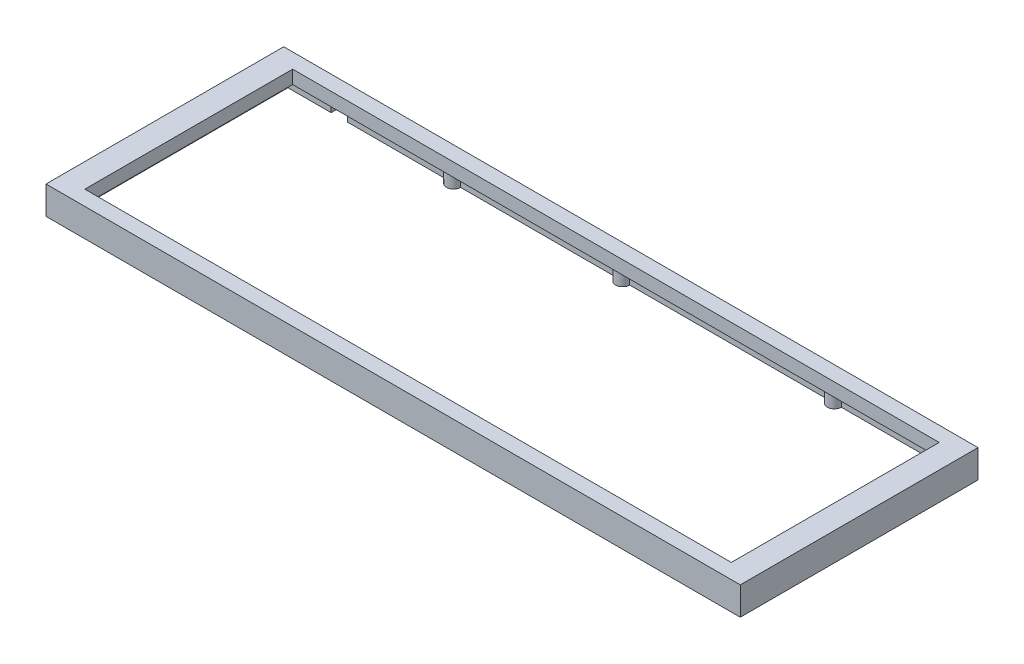
SolidWorks part; units mm, degrees
ref_plane "Front Plane" through (0, 0, 0) normal (0, 0, 1) x (1, 0, 0)
ref_plane "Top Plane" through (0, 0, 0) normal (0, 1, 0) x (1, 0, 0)
ref_plane "Right Plane" through (0, 0, 0) normal (1, 0, 0) x (0, 0, -1)
sketch "Sketch1" plane through (0, 0, 0) normal (0, 1, 0) x (1, 0, 0)
  line L1 (0, 0) -> (363.9, 0)
  line L2 (0, 0) -> (0, 117)
  line L3 (0, 117) -> (363.9, 117)
  line L4 (363.9, 0) -> (363.9, 117)
  line L5 (-13.44, 125.4) -> (377.34, 125.4)
  line L6 (-13.44, 125.4) -> (-13.44, -8.4)
  line L7 (-13.44, -8.4) -> (377.34, -8.4)
  line L8 (377.34, 125.4) -> (377.34, -8.4)
  dimension "D1" = 363.9
  dimension "D2" = 117
  dimension "D3" = 8.4
  dimension "D4" = 13.44
  dimension "D5" = 13.44
  dimension "D6" = 8.4
extrude "Boss-Extrude1" add sketch "Sketch1" along normal blind 7.5
sketch "Sketch2" plane through (0, 0, 0) normal (0, 1, 0) x (1, 0, 0)
  line L0 (-13.44, 125.4) -> (-13.44, -8.4) construction
  line L1 (-8.04, 122.4) -> (371.96, 122.4)
  line L2 (-8.04, 122.4) -> (-8.04, -6)
  line L3 (-8.04, -6) -> (371.96, -6)
  line L4 (371.96, 122.4) -> (371.96, -6)
  line L5 (377.34, 125.4) -> (-13.44, 125.4) construction
  point P6 (-13.44, 58.5)
  line M13 (-13.44, -8.4) -> (-13.44, 125.4)
  line M14 (-13.44, 125.4) -> (377.34, 125.4)
  line M15 (377.34, 125.4) -> (377.34, -8.4)
  line M16 (377.34, -8.4) -> (-13.44, -8.4)
  dimension "D1" = 380
  dimension "D2" = 128.4
  dimension "D3" = 5.4
  dimension "D4" = 3
extrude "Boss-Extrude2" add sketch "Sketch2" against normal blind 8.3 contours L4 L1 L2 L3 M16 M13 M14 M15 region at (-9.3095, 0, -58.5)
sketch "Sketch4" plane through (0, 0, -125.4) normal (0, 0, -1) x (-1, 0, 0)
  line L0 (13.44, -8.3) -> (-377.34, -8.3) construction
  line L1 (-25.46, -8.3) -> (-16.26, -8.3)
  line L2 (-25.46, -8.3) -> (-25.46, -3.3)
  line L3 (-25.46, -3.3) -> (-16.26, -3.3)
  line L4 (-16.26, -8.3) -> (-16.26, -3.3)
  line L6 (13.44, 7.5) -> (13.44, -8.3) construction
  dimension "D1" = 38.9
  dimension "D2" = 9.2
  dimension "D3" = 5
extrude "Cut-Extrude1" cut sketch "Sketch4" against normal blind 7.5
sketch "Sketch5" plane through (0, 0, 0) normal (0, -1, 0) x (1, 0, 0)
  line L6 (-8.04, -122.4) -> (371.96, -122.4) construction
  line L7 (-8.04, -122.4) -> (-8.04, 6) construction
  line L8 (25.46, -122.4) -> (371.96, -122.4) construction
  line L19 (-8.04, 6) -> (371.96, 6) construction
  line L25 (83.56, 6) -> (83.56, 0) construction
  line L31 (-8.04, 6) -> (371.96, 6) construction
  line L32 (274.06, 6) -> (274.06, 0) construction
  line L33 (80.39, 3) -> (86.73, 3)
  line L34 (80.39, 3) -> (80.39, 6)
  line L35 (80.39, 6) -> (86.73, 6)
  line L36 (86.73, 3) -> (86.73, 6)
  line L37 (270.89, 3) -> (277.23, 3)
  line L38 (270.89, 3) -> (270.89, 6)
  line L39 (270.89, 6) -> (277.23, 6)
  line L40 (277.23, 3) -> (277.23, 6)
  circle A0 centre (83.56, 3) radius 3.17
  circle A1 centre (274.06, 3) radius 3.17
  circle A2 centre (85.16, -122.4) radius 3.95
  circle A3 centre (180.36, -122.4) radius 3.95
  circle A4 centre (299.46, -122.4) radius 3.95
  point P2 (0, 0)
  line M20 (-8.04, -122.4) -> (371.96, -122.4)
  line M22 (371.96, 6) -> (-8.04, 6)
  line M25 (0, 0) -> (363.9, 0)
  dimension "D9" = 6.34
  dimension "D3" = 6.34
  dimension "D11" = 7.9
  dimension "D12" = 7.9
  dimension "D13" = 7.9
  dimension "D2" = 93.2
  dimension "D4" = 188.4
  dimension "D5" = 91.6
  dimension "D6" = 307.5
  dimension "D7" = 3
  dimension "D8" = 3
  dimension "D10" = 282.1
extrude "Boss-Extrude3" add sketch "Sketch5" along normal up to surface (8.3 mm away) contours A0 L33 M25 | L33 A0 L35 | A0 L34 M22 | A1 L37 M25 | L37 A1 L39 | A1 L40 M22 | A4 M20 | A3 M20 | A2 M20 | L35 L36 L33 L34 | L39 L40 L37 L38 region at (83.56, 0, 4.3195) region at (80.9653, 0, 5.3091) region at (83.56, 0, 1.6805) region at (274.06, 0, 1.6805) region at (274.06, 0, 4.3195) region at (276.6547, 0, 5.3091) region at (85.16, 0, -120.7236) region at (299.46, 0, -120.7236) region at (180.36, 0, -120.7236) up to face at (128.2567, -8.3, -80.2)
